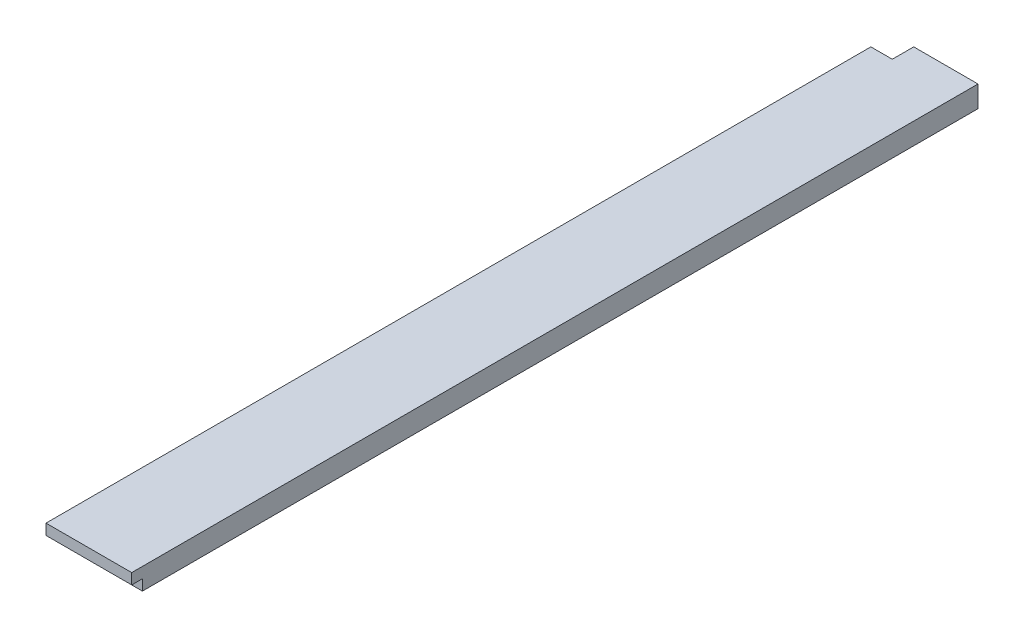
SolidWorks part; units mm, degrees
ref_plane "Front Plane" through (0, 0, 0) normal (0, 0, 1) x (1, 0, 0)
ref_plane "Top Plane" through (0, 0, 0) normal (0, 1, 0) x (1, 0, 0)
ref_plane "Right Plane" through (0, 0, 0) normal (1, 0, 0) x (0, 0, -1)
sketch "Sketch1" plane through (0, 0, 0) normal (0, 0, 1) x (1, 0, 0)
  line L0 (0, 12.7) -> (0, 6.35)
  line L1 (0, 6.35) -> (12.7, 6.35)
  line L2 (12.7, 6.35) -> (12.7, 0)
  line L3 (12.7, 0) -> (50.8, 0)
  line L4 (50.8, 0) -> (50.8, 12.7)
  line L5 (50.8, 12.7) -> (0, 12.7)
  dimension "D1" = 6.35
  dimension "D2" = 6.35
  dimension "D3" = 12.7
  dimension "D4" = 50.8
extrude "Boss-Extrude1" add sketch "Sketch1" along normal blind 501.65
sketch "Sketch2" plane through (0, 0, 0) normal (0, -1, 0) x (1, 0, 0)
  line L0 (50.8, 501.65) -> (50.8, 0) construction
  line L1 (50.8, 495.3) -> (12.7, 495.3)
  line L2 (50.8, 495.3) -> (50.8, 501.65)
  line L3 (50.8, 501.65) -> (12.7, 501.65)
  line L4 (12.7, 495.3) -> (12.7, 501.65)
  dimension "D1" = 6.35
extrude "Cut-Extrude1" cut sketch "Sketch2" against normal blind 6.35
sketch "Sketch3" plane through (0, 12.7, 0) normal (0, 1, 0) x (1, 0, 0)
  line L1 (0, 0) -> (12.7, 0)
  line L2 (0, 0) -> (0, -12.7)
  line L3 (0, -12.7) -> (12.7, -12.7)
  line L4 (12.7, 0) -> (12.7, -12.7)
  dimension "D1" = 12.7
  dimension "D2" = 12.7
extrude "Cut-Extrude2" cut sketch "Sketch3" against normal through all
